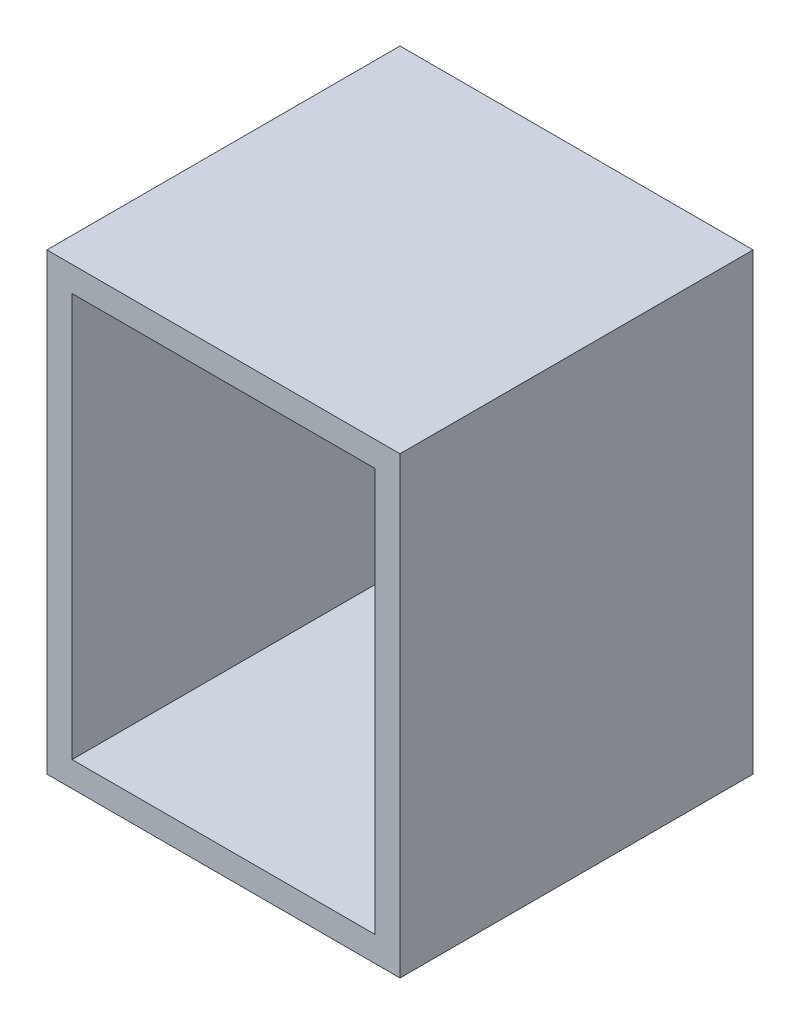
SolidWorks part; units mm, degrees
ref_plane "Front Plane" through (0, 0, 0) normal (0, 0, 1) x (1, 0, 0)
ref_plane "Top Plane" through (0, 0, 0) normal (0, 1, 0) x (1, 0, 0)
ref_plane "Right Plane" through (0, 0, 0) normal (1, 0, 0) x (0, 0, -1)
sketch "Sketch4" plane through (0, 0, 0) normal (0, 0, 1) x (1, 0, 0)
  line L1 (-20.2849, 20.5607) -> (14.7151, 20.5607)
  line L2 (-20.2849, 20.5607) -> (-20.2849, -24.4393)
  line L3 (-20.2849, -24.4393) -> (14.7151, -24.4393)
  line L4 (14.7151, 20.5607) -> (14.7151, -24.4393)
  dimension "D1" = 35
  dimension "D2" = 45
extrude "Boss-Extrude2" add sketch "Sketch4" along normal blind 35
sketch "Sketch5" plane through (0, 0, 35) normal (0, 0, 1) x (1, 0, 0)
  line L0 (-17.7849, 18.0607) -> (-17.7849, -21.9393)
  line L1 (-20.2849, 20.5607) -> (14.7151, 20.5607)
  line L2 (-20.2849, 20.5607) -> (-20.2849, -24.4393)
  line L3 (-20.2849, -24.4393) -> (14.7151, -24.4393)
  line L4 (14.7151, 20.5607) -> (14.7151, -24.4393)
  line L5 (-17.7849, -21.9393) -> (12.2151, -21.9393)
  line L6 (12.2151, 18.0607) -> (12.2151, -21.9393)
  line L7 (-17.7849, 18.0607) -> (12.2151, 18.0607)
  dimension "D1" = 2.5
extrude "Cut-Extrude1" cut sketch "Sketch5" against normal blind 32.5 flip side to cut
